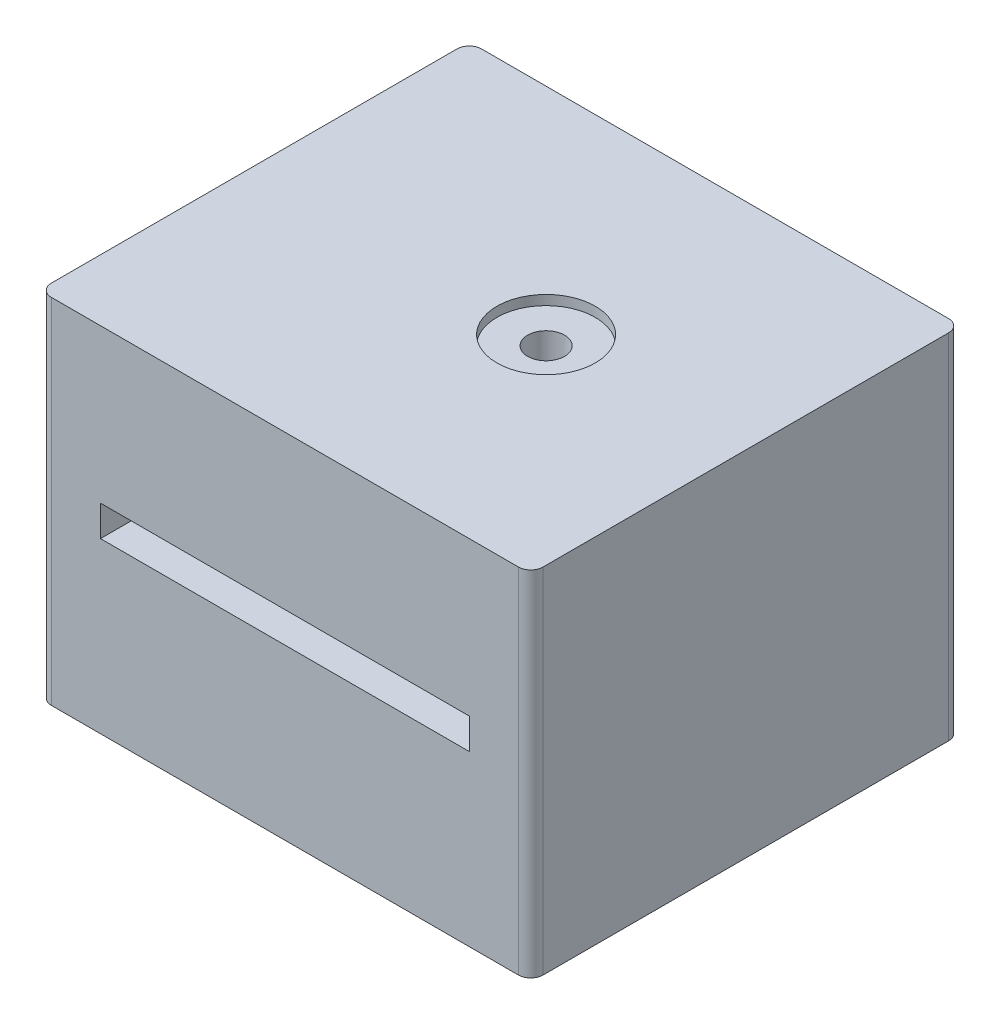
SolidWorks part; units mm, degrees
ref_plane "前视基准面" through (0, 0, 0) normal (0, 0, 1) x (1, 0, 0)
ref_plane "上视基准面" through (0, 0, 0) normal (0, 1, 0) x (1, 0, 0)
ref_plane "右视基准面" through (0, 0, 0) normal (1, 0, 0) x (0, 0, -1)
other "Configuration Table"
sketch "Sketch2" plane through (0, 0, 0) normal (0, 1, 0) x (1, 0, 0)
  line L1 (-80, -70) -> (80, -70)
  line L2 (-80, -70) -> (-80, 70)
  line L3 (-80, 70) -> (80, 70)
  line L4 (80, -70) -> (80, 70)
  point P4 (-80, 0)
  point P6 (0, 70)
  dimension "D1" = 140
  dimension "D2" = 160
extrude "BOX_EXTRUDE" add sketch "Sketch2" along normal blind 100 and the other way blind 15
sketch "Sketch3" plane through (0, 100, 0) normal (0, 1, 0) x (1, 0, 0)
  line L1 (-60, 50) -> (60, 50)
  line L2 (-60, 50) -> (-60, -50)
  line L3 (-60, -50) -> (60, -50)
  line L4 (60, 50) -> (60, -50)
  point P4 (0, 50)
  point P7 (-60, 0)
  dimension "D1" = 120
  dimension "D2" = 100
extrude "BOX_INNER_CUT" cut sketch "Sketch3" against normal blind 40 from offset 20 offset against normal yes
sketch "Sketch6" plane through (0, 100, 0) normal (0, 1, 0) x (1, 0, 0)
  line L0 (0, 30.656) -> (0, -17.5007) construction
  circle A0 centre (15, 0) radius 6
  circle A1 centre (-15, 0) radius 6
  dimension "D2" = 12
  dimension "D1" = 15
extrude "SHAFT_CUT" cut sketch "Sketch6" against normal blind 40 from offset 60 offset against normal yes
sketch "Sketch9" plane through (0, 100, 0) normal (0, 1, 0) x (1, 0, 0)
  circle A0 centre (15, 0) radius 8
  circle A2 centre (-15, 0) radius 16
  dimension "D1" = 16
  dimension "D2" = 32
extrude "BEARING_CUTS_INSIDE_BOX" cut sketch "Sketch9" against normal blind 10 from offset 60 offset against normal yes
sketch "Sketch11" plane through (0, 0, 70) normal (0, 0, 1) x (1, 0, 0)
  line L0 (-80, -15) -> (80, -15) construction
  line L1 (-60, 50) -> (60, 50)
  line L2 (-60, 50) -> (-60, 40)
  line L3 (-60, 40) -> (60, 40)
  line L4 (60, 50) -> (60, 40)
  point P4 (0, 50)
  dimension "D1" = 120
  dimension "D2" = 10
  dimension "D3" = 55
extrude "SCISSOR_CUT" cut sketch "Sketch11" against normal blind 20
sketch "Sketch12" plane through (0, 100, 0) normal (0, 1, 0) x (1, 0, 0)
  circle A0 centre (15, 0) radius 16
  dimension "D1" = 32
extrude "MOTOR_HOLE_CUT" cut sketch "Sketch12" against normal blind 3.15
sketch "Sketch15" plane through (0, 96.85, 0) normal (0, 1, 0) x (1, 0, 0)
  circle A0 centre (15, 0) radius 6
  dimension "D1" = 12
extrude "RIGHT_SHAFT_LID_CUT" cut sketch "Sketch15" against normal up to next
sketch "Sketch18" plane through (0, 100, 0) normal (0, 1, 0) x (1, 0, 0)
  circle A0 centre (-15, 0) radius 8
  dimension "D1" = 16
extrude "LEFT_BEARING_LID_CUT" cut sketch "Sketch18" against normal blind 10 from offset 10 offset against normal yes
fillet "OUTER_EDGES_FILLET" radius 4 4 edges at (-80, 42.5, -70) (80, 42.5, -70) (80, 42.5, 70) (-80, 42.5, 70)
